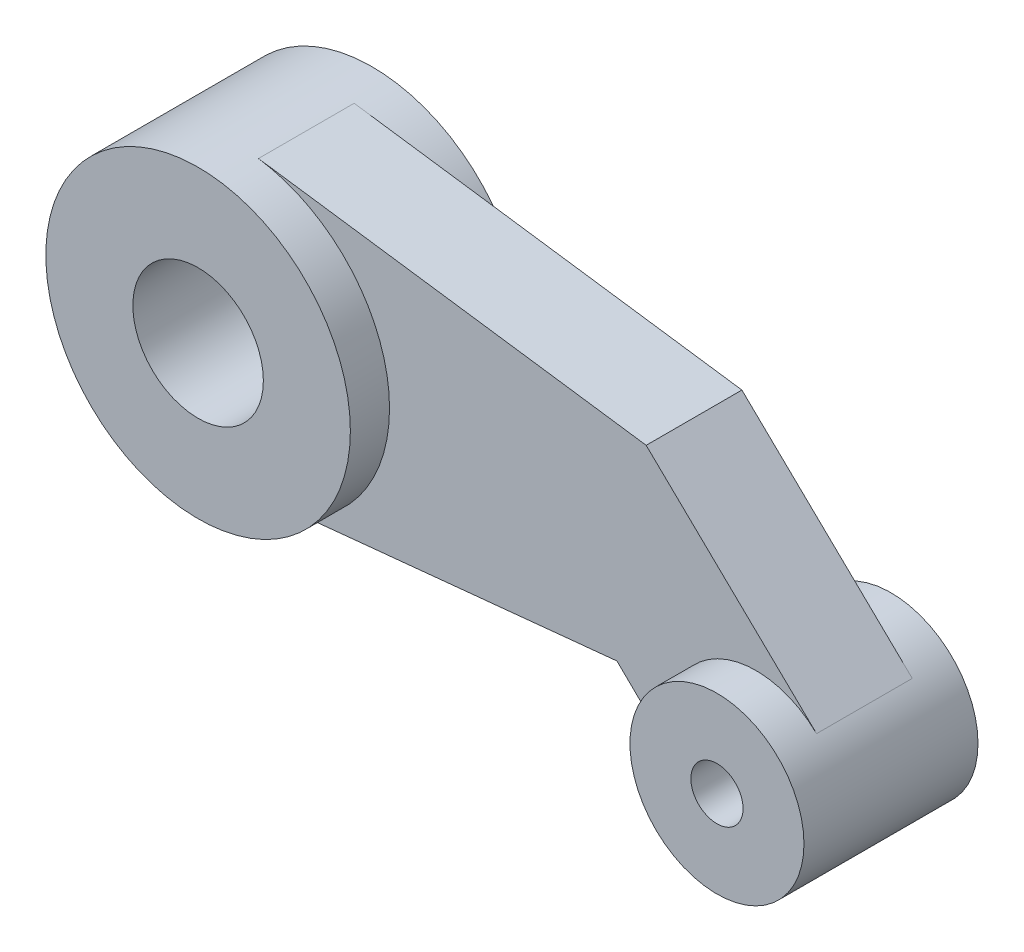
SolidWorks part; units mm, degrees
ref_plane "Plan de face" through (0, 0, 0) normal (0, 0, 1) x (1, 0, 0)
ref_plane "Plan de dessus" through (0, 0, 0) normal (0, 1, 0) x (1, 0, 0)
ref_plane "Plan de droite" through (0, 0, 0) normal (1, 0, 0) x (0, 0, -1)
sketch "Esquisse1" plane through (0, 0, 0) normal (0, 0, 1) x (1, 0, 0)
  line L0 (2.4355, 17.3297) -> (46.9976, 11.0669)
  line L1 (46.9976, 11.0669) -> (66.579, -7.8426)
  line L2 (0, 17.5) -> (47.4788, 17.5) construction
  line L3 (-7.5, 0) -> (46.9976, 11.0669) construction
  line L4 (7.8109, -15.6601) -> (43.6324, -12.0796)
  line L5 (43.6324, -12.0796) -> (50.2733, -18.5583)
  line L7 (-7.5, 0) -> (43.6324, -12.0796) construction
  circle A0 centre (0, 0) radius 17.5
  circle A1 centre (0, 0) radius 7.5
  circle A2 centre (59.6324, -15.036) radius 3
  circle A3 centre (59.6324, -15.036) radius 10
  point P11 (0, -17.5)
  point P12 (32.8359, -11.2618)
  point P17 (0, -18.8698)
  point P18 (0, -22.2225)
  point P20 (2.4355, -17.3297)
  point P21 (37.4504, 8.1162)
  point P22 (61.8344, -11.7556)
  point P23 (43.023, -17.3002)
  point P24 (33.465, 0)
  point P25 (33.3114, 0)
  point P26 (40.315, -22.2225)
  point P27 (13.672, -10.9237)
  point P28 (36.5755, -13.7118)
  point P29 (47.4788, 11.0669)
  point P30 (61.4781, -11.9834)
  point P31 (66.4098, -8.0163)
  dimension "D1" = 6
  dimension "D2" = 20
  dimension "D3" = 15
  dimension "D4" = 35
  dimension "D6" = 8
  dimension "D10" = 16
  dimension "D5" = 45
  dimension "D7" = 29
  dimension "D8" = 36
  dimension "D9" = 19
  dimension "D11" = 36
  dimension "D12" = 50
extrude "Boss.-Extru.1" add sketch "Esquisse1" along normal blind 11 contours A3 L1 L0 A0 L4 L5 | A0 A1 | A3 A2 region at (33.9146, -0.4057, 0) region at (12.8339, 11.1563, 0) region at (68.5771, -11.2392, 0)
extrude "Boss.-Extru.2" add sketch "Esquisse1<3>" along normal blind 15.5 and the other way blind 4.5 contours A1 | A2 | A0 | A3 region at (0, 0, 0) region at (59.6324, -15.036, 0)
sketch "Esquisse1<3>" plane through (0, 0, 0) normal (0, 0, 1) x (1, 0, 0) same geometry as "Esquisse1"
